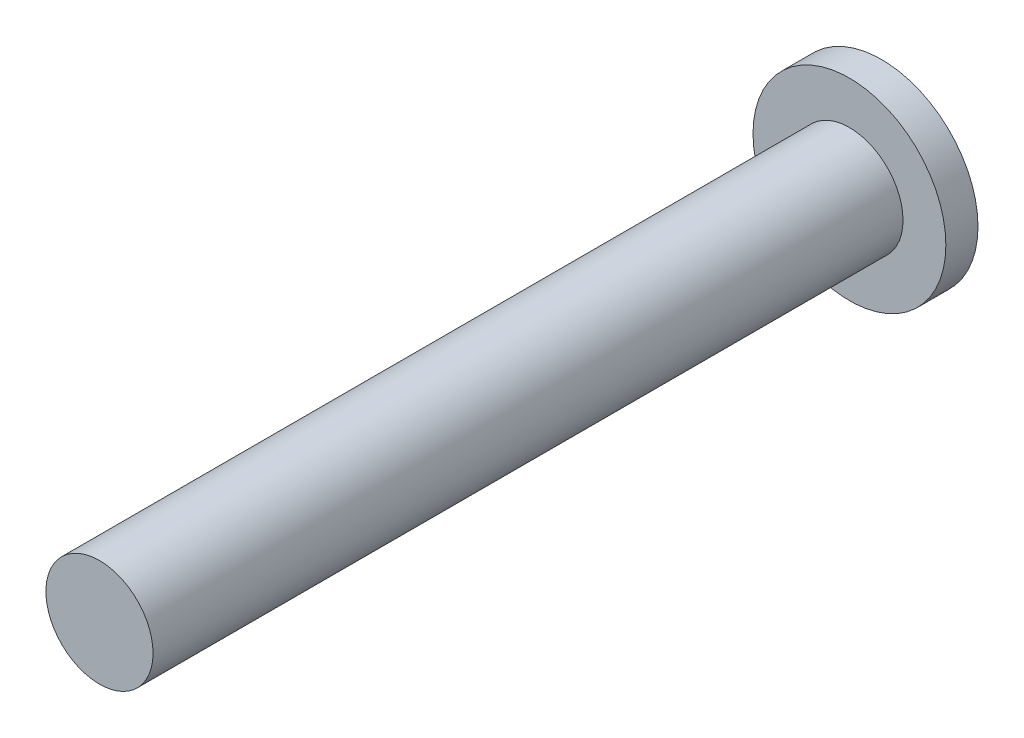
SolidWorks part; units mm, degrees
material "Stainless Steel (ferritic)"
ref_plane "Front Plane" through (0, 0, 0) normal (0, 0, 1) x (1, 0, 0)
ref_plane "Top Plane" through (0, 0, 0) normal (0, 1, 0) x (1, 0, 0)
ref_plane "Right Plane" through (0, 0, 0) normal (1, 0, 0) x (0, 0, -1)
sketch "Sketch1" plane through (0, 0, 0) normal (0, 0, 1) x (1, 0, 0)
  circle A0 centre (0, 0) radius 4.5
  circle A1 centre (0, 0) radius 2.5
  dimension "D1" = 9
  dimension "D2" = 5
extrude "Boss-Extrude1" add sketch "Sketch1" against normal blind 1.5 contours A0 A1 | A1 region at (-4.3727, 0, 0) region at (0, 0, 0)
extrude "Boss-Extrude2" add sketch "Sketch1<3>" along normal blind 35 contours A1 region at (0, 0, 0)
sketch "Sketch1<3>" plane through (0, 0, 0) normal (0, 0, 1) x (1, 0, 0) same geometry as "Sketch1"
